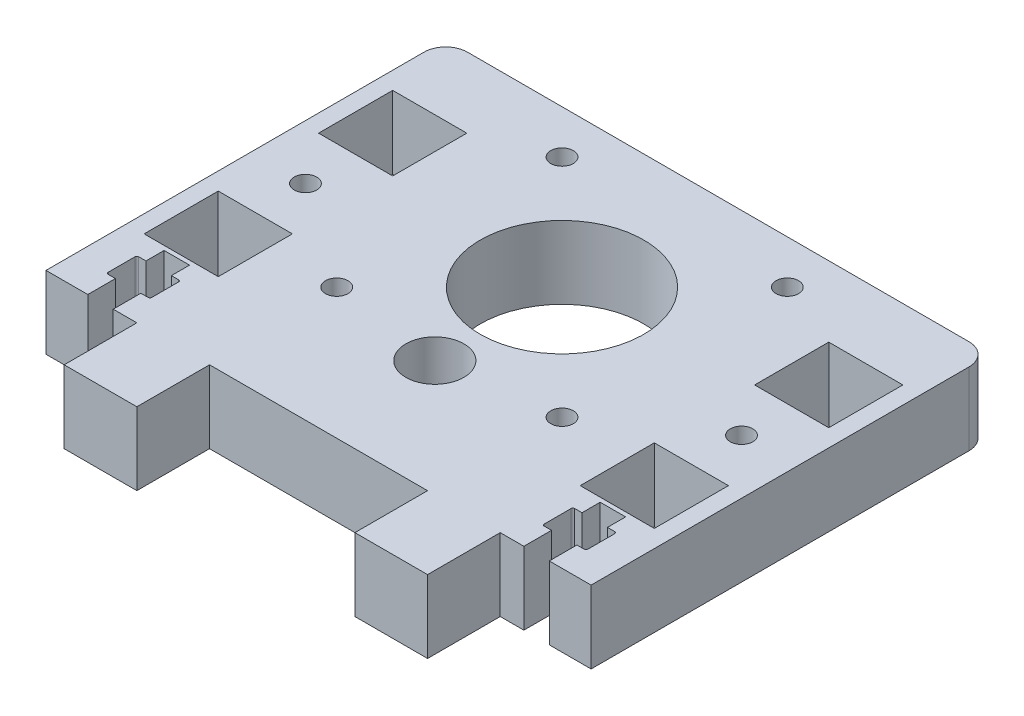
SolidWorks part; units mm, degrees
ref_plane "Front Plane" through (0, 0, 0) normal (0, 0, 1) x (1, 0, 0)
ref_plane "Top Plane" through (0, 0, 0) normal (0, 1, 0) x (1, 0, 0)
ref_plane "Right Plane" through (0, 0, 0) normal (1, 0, 0) x (0, 0, -1)
sketch "Sketch1" plane through (0, 0, 0) normal (0, 1, 0) x (1, 0, 0)
  line L0 (0, 29) -> (0, -6) construction
  line L1 (-34.5, 29) -> (0, 29)
  line L2 (-37.5, 26) -> (-37.5, -26)
  line L3 (-37.5, -26) -> (-25, -26)
  line L4 (0, 29) -> (0, 18.75)
  line L5 (0, -3.75) -> (0, -6)
  line L6 (0, -14) -> (0, -26) construction
  line L7 (-11.25, 7.5) -> (0, 7.5) construction
  line L8 (0, -14) -> (0, -26)
  line L9 (-30, 19.3) -> (-30, 9.1) construction
  line L10 (-37.5, 2.2) -> (0, 2.2) construction
  line L11 (-35.1, 19.3) -> (-24.9, 19.3)
  line L12 (-35.1, 19.3) -> (-35.1, 9.1)
  line L13 (-35.1, 9.1) -> (-24.9, 9.1)
  line L14 (-24.9, 19.3) -> (-24.9, 9.1)
  line L15 (-35.1, 19.3) -> (-24.9, 9.1) construction
  line L16 (-35.1, 9.1) -> (-24.9, 19.3) construction
  line L17 (-35.1, -4.7) -> (-24.9, -14.9) construction
  line L18 (-35.1, -14.9) -> (-24.9, -4.7) construction
  line L19 (-24.9, -14.9) -> (-24.9, -4.7)
  line L20 (-35.1, -4.7) -> (-24.9, -4.7)
  line L21 (-35.1, -14.9) -> (-35.1, -4.7)
  line L22 (-35.1, -14.9) -> (-24.9, -14.9)
  line L23 (-30, -4.7) -> (-30, -14.9) construction
  line L24 (-30, -9.8) -> (-30, 14.2) construction
  line L25 (0, 7.5) -> (-15.5, 23) construction
  line L35 (-15, -26) -> (0, -26)
  line L43 (-20, -36) -> (-20, -26.9) construction
  line L44 (-15, -26) -> (-15, -36)
  line L45 (-15, -36) -> (-25, -36)
  line L46 (-25, -36) -> (-25, -26)
  arc A1 (-34.5, 29) -> (-37.5, 26) centre (-34.5, 26) ccw
  arc A2 (0, 18.75) -> (0, -3.75) centre (0, 7.5) ccw
  circle A4 centre (-15.5, 23) radius 1.55
  circle A6 centre (-15.5, -8) radius 1.55
  circle A7 centre (-30, 2.2) radius 1.55
  arc A10 (0, -6) -> (0, -14) centre (0, -10) ccw
  point P0 (0, 0)
  point P28 (-30, 14.2)
  point P39 (-30, -9.8)
  dimension "D7" = 22.5
  dimension "D17" = 8
  dimension "D14" = 3.1
  dimension "D6" = 3
  dimension "D19" = 3.1
  dimension "D1" = 55
  dimension "D9" = 10.2
  dimension "D10" = 10.2
  dimension "D22" = 10
  dimension "D23" = 10
  dimension "D16" = 17.5
  dimension "D11" = 24
  dimension "D13" = 2.2
  dimension "D3" = 37.5
  dimension "D4" = 31
  dimension "D5" = 15.5
  dimension "D15" = 26
  dimension "D18" = 37.5
  dimension "D20" = 20
  dimension "D8" = 16
  dimension "D12" = 30
extrude "MainLayout" add sketch "Sketch1" along normal blind 10
sketch "Sketch2" plane through (0, 10, 0) normal (0, 1, 0) x (1, 0, 0)
  line L0 (-30, -26) -> (-30, -15.5) construction
  line L1 (-28.25, -22.2) -> (-28.25, -26)
  line L2 (-37.5, -26) -> (-25, -26) construction
  line L3 (-28.25, -15.5) -> (-31.75, -15.5)
  line L4 (-31.75, -15.5) -> (-31.75, -18)
  line L5 (-31.75, -18) -> (-32.75, -18)
  line L6 (-33, -18.25) -> (-33, -21.95)
  line L7 (-32.75, -22.2) -> (-31.75, -22.2)
  line L8 (-31.75, -22.2) -> (-31.75, -26)
  line L9 (-31.75, -26) -> (-28.25, -26)
  line L10 (-27.25, -22.2) -> (-28.25, -22.2)
  line L11 (-27, -18.25) -> (-27, -21.95)
  line L12 (-28.25, -18) -> (-27.25, -18)
  line L13 (-28.25, -15.5) -> (-28.25, -18)
  line L14 (0, -26) -> (0, -14) construction
  line L30 (-30, -26) -> (-30, -15.5) construction
  arc A0 (-27, -18.25) -> (-27.25, -18) centre (-27.25, -18.25) ccw
  arc A1 (-32.75, -18) -> (-33, -18.25) centre (-32.75, -18.25) ccw
  arc A2 (-27.25, -22.2) -> (-27, -21.95) centre (-27.25, -21.95) ccw
  arc A3 (-33, -21.95) -> (-32.75, -22.2) centre (-32.75, -21.95) ccw
  point P17 (0, -20)
  point P38 (-27, -18)
  point P41 (-33, -18)
  point P44 (-27, -22.2)
  point P47 (-33, -22.2)
  dimension "D8" = 0.25
  dimension "D1" = 1.75
  dimension "D2" = 0
  dimension "D3" = 4.2
  dimension "D5" = 10.5
  dimension "D6" = 3
  dimension "D4" = 8
  dimension "D7" = 30
extrude "TSlot" cut sketch "Sketch2" against normal through all
mirror "Mirror1" about plane through (0, 0, 0) normal (1, 0, 0) of "TSlot", "MainLayout"
equation "\"Y-ROD-SPACING\"=75"
equation "\"Y-BED-OFFSET\"=2"
equation "\"Y-BED-ROD-INSET\"=3.5"
equation "\"T-SLOT-NUT-FILLET-RADIUS\"=0.25"
equation "\"T-SLOT-SCREW-SHAFT-RADIUS\"=1.75"
equation "\"T-SLOT-SCREW-SHAFT-CUTOUT-LENGTH\"=10.5"
equation "\"T-SLOT-NUT-DEPTH\"=4.2"
equation "\"T-SLOT-NUT-WIDTH\"=3"
equation "\"T-SLOT-NUT-END-DISTANCE\"=8"
equation "\"ACRYLIC-TAB-CUTOUT-SIZE\"=\"ACRYLIC-THICKNESS\"+\"ACRYLIC-TAB-TOLERANCE\"*2"
equation "\"ACRYLIC-TAB-WIDTH\"=\"ACRYLIC-THICKNESS\""
equation "\"ACRYLIC-M3-HOLE\"=3.1"
equation "\"SMOOTHROD-CAP-SCREW-DISTANCE\"=20"
equation "\"FRAME-WIDTH-INNER\"=370"
equation "\"NEMA17-HOLE-SPACING\"=31"
equation "\"NEMA17-CENTRAL-CUTOUT\"=22.5"
equation "\"D7@Sketch1\"=\"NEMA17-CENTRAL-CUTOUT\""
equation "\"D5@Sketch1\"=\"NEMA17-HOLE-SPACING\"/2"
equation "\"D4@Sketch1\"=\"NEMA17-HOLE-SPACING\""
equation "\"D19@Sketch1\"=\"ACRYLIC-M3-HOLE\""
equation "\"D14@Sketch1\"=\"ACRYLIC-M3-HOLE\""
equation "\"D9@Sketch1\"=\"ACRYLIC-TAB-CUTOUT-SIZE\""
equation "\"D10@Sketch1\"=\"ACRYLIC-TAB-CUTOUT-SIZE\""
equation "\"D23@Sketch1\"=\"ACRYLIC-TAB-WIDTH\""
equation "\"D22@Sketch1\"=\"ACRYLIC-TAB-WIDTH\""
equation "\"D5@Sketch2\"=\"T-SLOT-SCREW-SHAFT-CUTOUT-LENGTH\""
equation "\"D4@Sketch2\"=\"T-SLOT-NUT-END-DISTANCE\""
equation "\"D3@Sketch2\"=\"T-SLOT-NUT-DEPTH\""
equation "\"D1@Sketch2\"=\"T-SLOT-SCREW-SHAFT-RADIUS\""
equation "\"D8@Sketch2\"=\"T-SLOT-NUT-FILLET-RADIUS\""
equation "\"Z-BRACKET-REACH\"=55"
equation "\"D1@Sketch1\"=\"Z-BRACKET-REACH\""
equation "\"Z-ROD-SPACING\"=17.5"
equation "\"ACRYLIC-THICKNESS\"=10"
equation "\"TOP-BRACKET-SPACING\"=40"
equation "\"SMOOTHROD-X-LENGTH\"=350"
equation "\"SMOOTHROD-Y-LENGTH\"=350"
equation "\"SMOOTHROD-Z-LENGTH\"=350"
equation "\"SMOOTHROD-TIGHTENING-HEADROOM\"=.25"
equation "\"LEADSCREW-Z-LENGTH\"=300"
equation "\"D16@Sketch1\"=\"Z-ROD-SPACING\""
equation "\"X-ROD-SPACING\"=45"
equation "\"ACRYLIC-THICKNESS2\"=4.5"
equation "\"SCREW-LENGTH-FRAME\"=\"ACRYLIC-THICKNESS\" + 10"
equation "\"SCREW-HEAD-RADIUS\"=6"
equation "\"PRINTED-X-SMOOTHROD-DIAMETER\"=8.2"
equation "\"PRINTED-X-SMOOTHROD-CUTOUT\"=10"
equation "\"PRINTED-X-BASE-HEIGHT\"=10"
equation "\"PRINTED-LM8UU-CUTOUT-SIZE\"=15.25"
equation "\"PRINTED-LM8UU-CUTOUT-LENGTH\"=24.5"
equation "\"PRINTED-X-IDLER-HEIGHT\"=16"
equation "\"PSU-MOUNTING-WIDTH\"=95"
equation "\"PSU-MOUNTING-HEIGHT\"=177"
equation "\"D1@MainLayout\"=\"ACRYLIC-THICKNESS\""
equation "\"Z-ROD-INSET\"=16"
equation "\"Y-BELT-TO-ROD-DISTANCE\"=20"
equation "\"SPOOL-HOLDER-ROD-SPACING\"=150"
equation "\"D8@Sketch1\"=\"Z-ROD-INSET\""
equation "\"Y-BED-SCREW-SPACING\"=209"
equation "\"Y-BED-SCREW-CUTOUT-SLOT-HEIGHT\"=2"
equation "\"ACRYLIC-TAB-TOLERANCE\"=.1"
equation "\"SCREW-LENGTH-MOTOR\"=\"ACRYLIC-THICKNESS\" + 5"
equation "\"SCREW-LENGTH-EXTRUDER\"=28"
equation "\"ACRYLIC-X-CARRIAGE-WIDTH\"=55"
equation "\"ACRYLIC-X-CARRIAGE-HEIGHT\"=75"
equation "\"ACRYLIC-X-CARRIAGE-LM8UU-CUTOUT-WIDTH\"=24.25"
equation "\"ACRYLIC-X-CARRIAGE-SCREW-SPACING-X\"=15"
equation "\"ACRYLIC-X-CARRIAGE-SCREW-SPACING-Y\"=33"
equation "\"ACRYLIC-X-CARRIAGE-CENTER-TAB-SPACING\"=14"
equation "\"ACRYLIC-X-CARRIAGE-EXTRUDER-OFFSET\"=26"
equation "\"ACRYLIC-X-CARRIAGE-EXTRUDER-ANGLE\"=90"
equation "\"ACRYLIC-X-CARRIAGE-EXTRUDER-SHELF-DEPTH\"=\"ACRYLIC-X-CARRIAGE-EXTRUDER-OFFSET\" + 28"
equation "\"ACRYLIC-X-CARRIAGE-EXTRUDER-BRACE-SPACING\"=23"
equation "\"ACRYLIC-X-CARRIAGE-EXTRUDER-BRACE-TAB-OFFSET\"=20"
equation "\"ACRYLIC-X-CARRIAGE-EXTRUDER-BRACE-HEIGHT\"=35"
equation "\"ACRYLIC-X-CARRIAGE-EXTRUDER-BRACE-SCREW-SPACING\"=22"
